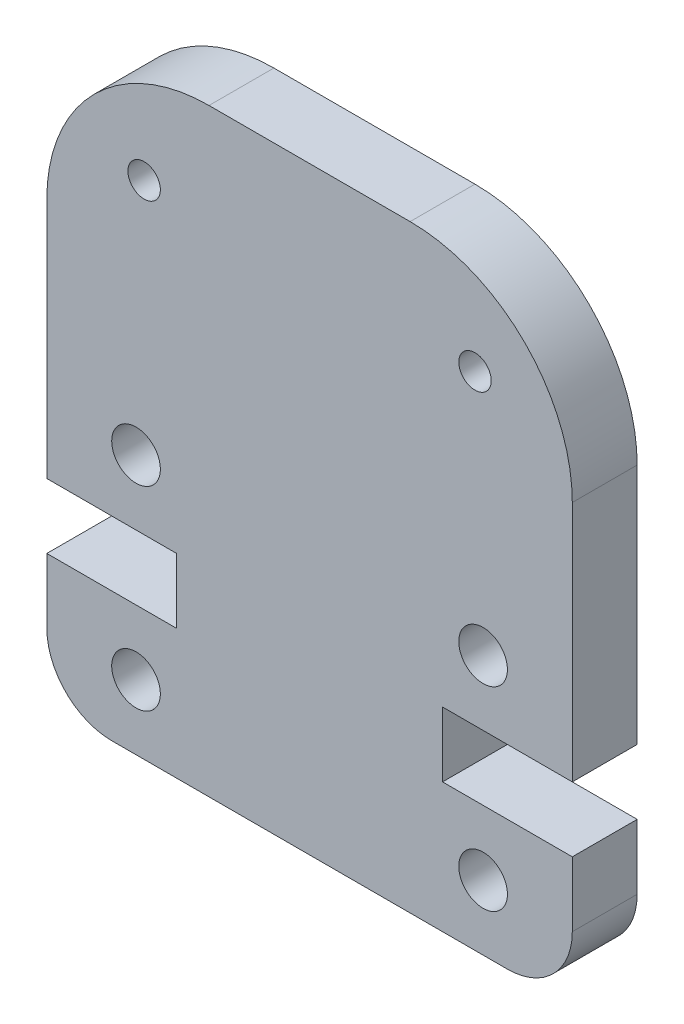
SolidWorks part; units mm, degrees
ref_plane "Front Plane" through (0, 0, 0) normal (0, 0, 1) x (1, 0, 0)
ref_plane "Top Plane" through (0, 0, 0) normal (0, 1, 0) x (1, 0, 0)
ref_plane "Right Plane" through (0, 0, 0) normal (1, 0, 0) x (0, 0, -1)
sketch "Sketch2" plane through (0, 0, 0) normal (0, 0, 1) x (1, 0, 0)
  line L0 (0, 13.46) -> (0, 6)
  line L1 (16.2, 13.46) -> (16.2, 6)
  line L12 (5, 18.46) -> (11.2, 18.46)
  line L13 (2, 0) -> (14.2, 0)
  line L16 (16.2, 2) -> (16.2, 4)
  line L17 (0, 2) -> (0, 4)
  line L18 (0, 6) -> (4, 6)
  line L19 (12.2, 4) -> (16.2, 4)
  line L20 (4, 6) -> (4, 4)
  line L21 (4, 4) -> (0, 4)
  line L22 (12.2, 6) -> (12.2, 4)
  line L23 (16.2, 6) -> (12.2, 6)
  arc A10 (14.2, 0) -> (16.2, 2) centre (14.2, 2) ccw
  arc A11 (5, 18.46) -> (0, 13.46) centre (5, 13.46) ccw
  arc A12 (16.2, 13.46) -> (11.2, 18.46) centre (11.2, 13.46) ccw
  circle A13 centre (3, 15.46) radius 0.5
  circle A14 centre (13.2, 15.46) radius 0.5
  arc A15 (0, 2) -> (2, 0) centre (2, 2) ccw
  circle A16 centre (13.45, 2) radius 0.75
  circle A17 centre (2.75, 2) radius 0.75
  circle A18 centre (2.75, 8) radius 0.75
  circle A19 centre (13.45, 8) radius 0.75
extrude "Boss-Extrude1" add sketch "Sketch2" along normal blind 2
